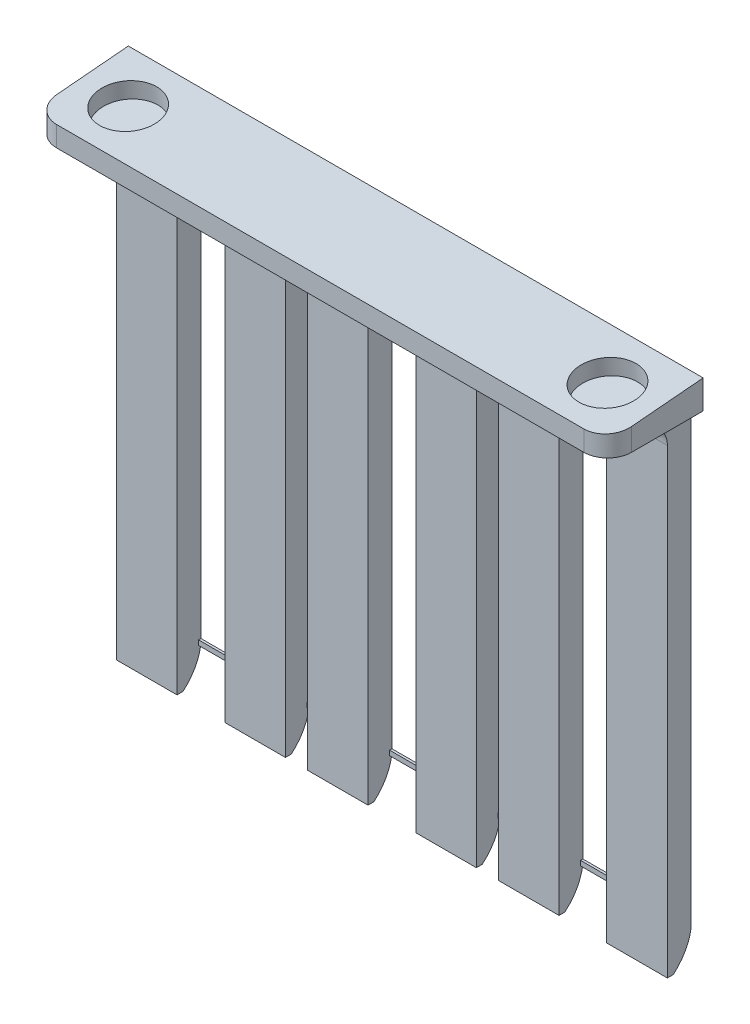
SolidWorks part; units mm, degrees
note: The reader was unsure of these and kept them because the rebuilt part matched: shared geometry of "Sketch1<3>".
ref_plane "Front Plane" through (0, 0, 0) normal (0, 0, 1) x (1, 0, 0)
ref_plane "Top Plane" through (0, 0, 0) normal (0, 1, 0) x (1, 0, 0)
ref_plane "Right Plane" through (0, 0, 0) normal (1, 0, 0) x (0, 0, -1)
sketch "Sketch1" plane through (0, 0, 0) normal (0, 0, 1) x (1, 0, 0)
  line L0 (25.2, 0) -> (37.9, 0)
  line L1 (0, 0) -> (120.4, 0)
  line L2 (0, 0) -> (0, 6)
  line L3 (0, 6) -> (120.4, 6)
  line L4 (120.4, 0) -> (120.4, 6)
  line L5 (2.5, 0) -> (15.2, 0)
  line L6 (2.5, 0) -> (2.5, -101.6)
  line L7 (2.5, -101.6) -> (15.2, -101.6)
  line L8 (15.2, 0) -> (15.2, -101.6)
  line L9 (25.2, 0) -> (25.2, -101.6)
  line L10 (25.2, -101.6) -> (37.9, -101.6)
  line L11 (37.9, 0) -> (37.9, -101.6)
  line L12 (65.2, 0) -> (77.9, 0)
  line L13 (42.5, 0) -> (55.2, 0)
  line L14 (42.5, 0) -> (42.5, -101.6)
  line L15 (42.5, -101.6) -> (55.2, -101.6)
  line L16 (55.2, 0) -> (55.2, -101.6)
  line L17 (65.2, 0) -> (65.2, -101.6)
  line L18 (65.2, -101.6) -> (77.9, -101.6)
  line L19 (77.9, 0) -> (77.9, -101.6)
  line L20 (20.2, -1084.3751) -> (20.2, 48915.6249) construction
  line L22 (25.2, 0) -> (65.2, 0) construction
  line L23 (105.2, 0) -> (117.9, 0)
  line L24 (82.5, 0) -> (95.2, 0)
  line L25 (82.5, 0) -> (82.5, -101.6)
  line L26 (82.5, -101.6) -> (95.2, -101.6)
  line L27 (95.2, 0) -> (95.2, -101.6)
  line L28 (105.2, 0) -> (105.2, -101.6)
  line L29 (105.2, -101.6) -> (117.9, -101.6)
  line L30 (117.9, 0) -> (117.9, -101.6)
  line L31 (65.2, 0) -> (105.2, 0) construction
  line L32 (2.5, 0) -> (25.2, 0) construction
  dimension "D2" = 6
  dimension "D3" = 101.6
  dimension "D4" = 12.7
  dimension "D6" = 2
  dimension "D7" = 5
  dimension "D8" = 40
  dimension "D10" = 40
  dimension "D11" = 22.7
  dimension "D12" = 2.5
  dimension "D13" = 2.5
  dimension "D5" = 2
  dimension "D9" = 2
extrude "Boss-Extrude1" add sketch "Sketch1" along normal blind 5
extrude "Boss-Extrude2" add sketch "Sketch1<3>" along normal blind 20 contours L1 L4 L3 L2 L0
sketch "Sketch1<3>" plane through (0, 0, 0) normal (0, 0, 1) x (1, 0, 0) same geometry as "Sketch1"
ref_plane "Plane1" through (117.9, 0, 0) normal (1, 0, 0) x (0, 0, -1)
sketch "Sketch2" plane through (117.9, 0, 0) normal (1, 0, 0) x (0, 0, -1)
  line L2 (-3.7714, -101.6) -> (0, -101.6)
  line L3 (0, -101.6) -> (0, -94.8605)
  arc A0 (-3.7714, -101.6) -> (0, -94.8605) centre (-10.6347, -93.3343) ccw
extrude "Cut-Extrude1" cut sketch "Sketch2" against normal through all
fillet "Fillet1" radius 5 1 edges at (111.55, 0, 5)
ref_plane "Plane3" through (120.4, 0, 0) normal (1, 0, 0) x (0, 0, -1)
sketch "Sketch4" plane through (120.4, 0, 0) normal (1, 0, 0) x (0, 0, -1)
  line L0 (0, 6) -> (-20, 4.2502)
  line L1 (-20, 6) -> (0, 6) construction
  line L2 (-20, 6) -> (-20, 4.2502)
  line L3 (-20, 0) -> (-20, 6) construction
  line L4 (-20, 6) -> (0, 6)
  dimension "D1" = 5
extrude "Cut-Extrude6" cut sketch "Sketch4" against normal through all
ref_plane "Plane4" through (0, 5.9544, 0.5209) normal (0, 0.9962, 0.0872) x (1, 0, 0)
sketch "Sketch5" plane through (0, 5.9544, 0.5209) normal (0, 0.9962, 0.0872) x (1, 0, 0)
  line L0 (0, -19.5535) -> (120.4, -19.5535) construction
  line L2 (120.4, -19.5535) -> (120.4, 0.5229) construction
  line L3 (0, -19.5535) -> (0, 0.5229) construction
  circle A0 centre (110.4, -9.5535) radius 6
  circle A1 centre (10, -9.5535) radius 6
  point P8 (120.4, -9.7664)
  dimension "D1" = 12
  dimension "D2" = 12
  dimension "D3" = 10
  dimension "D4" = 10
  dimension "D5" = 10
  dimension "D6" = 10
extrude "Cut-Extrude7" cut sketch "Sketch5" against normal blind 3.5
fillet "Fillet2" radius 5 2 edges at (120.4, 2.1251, 20) (0, 2.1251, 20)
sketch "Sketch6" plane through (0, 0, 0) normal (0, 0, 1) x (1, 0, 0)
  line L0 (2.5, 0) -> (2.5, -94.8605) construction
  line L1 (2.5, -94.8605) -> (117.9, -94.8605)
  line L2 (2.5, -94.8605) -> (2.5, -93.8605)
  line L3 (2.5, -93.8605) -> (117.9, -93.8605)
  line L4 (117.9, -94.8605) -> (117.9, -93.8605)
  line L5 (117.9, 0) -> (117.9, -94.8605) construction
  dimension "D1" = 1
extrude "Boss-Extrude3" add sketch "Sketch6" along normal blind 0.5
